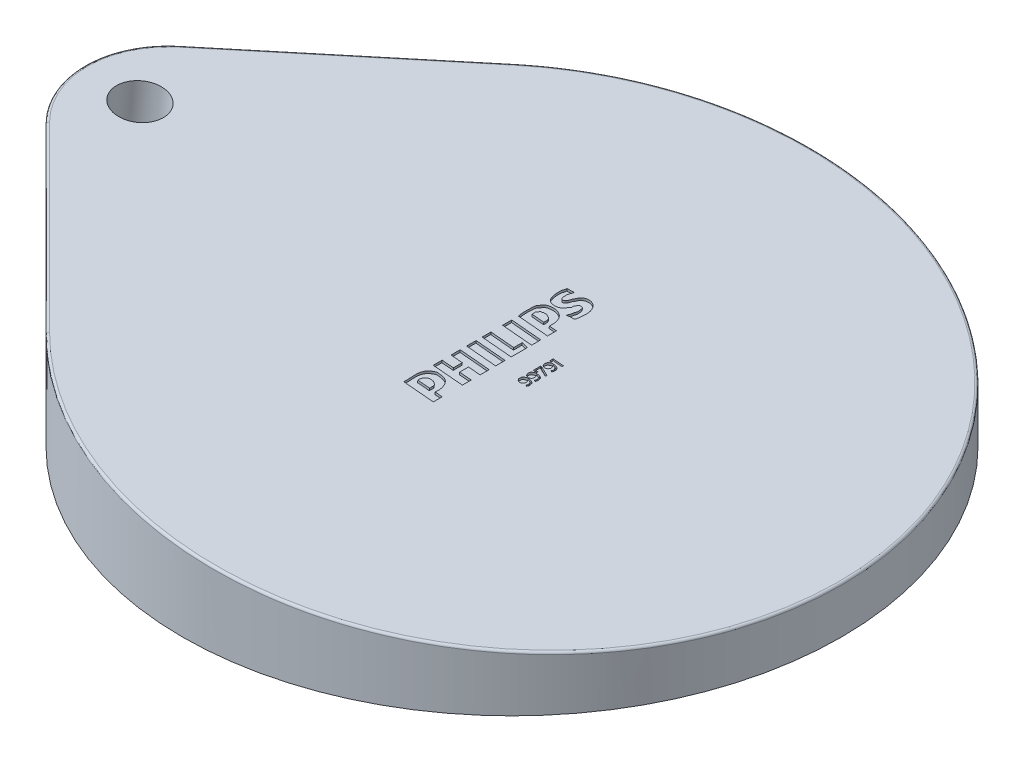
SolidWorks part; units mm, degrees
material "Copper"
ref_plane "Front Plane" through (0, 0, 0) normal (0, 0, 1) x (1, 0, 0)
ref_plane "Top Plane" through (0, 0, 0) normal (0, 1, 0) x (1, 0, 0)
ref_plane "Right Plane" through (0, 0, 0) normal (1, 0, 0) x (0, 0, -1)
sketch "Sketch14" plane through (0, 0, 0) normal (0, 0, 1) x (1, 0, 0)
  line L0 (0, -70) -> (-50, -70)
  line L1 (-70, 0) -> (-70, -50)
  line L2 (-69.75, 0) -> (-69.75, -49.75)
  line L3 (-49.75, -69.75) -> (0, -69.75)
  arc A0 (0, -70) -> (-70, 0) centre (0, 0) ccw
  arc A1 (-50, -70) -> (-70, -50) centre (-50, -50) cw
  circle A2 centre (-50, -50) radius 5
  arc A3 (0, -69.75) -> (-69.75, 0) centre (0, 0) ccw
  arc A4 (-69.75, -49.75) -> (-49.75, -69.75) centre (-49.75, -49.75) ccw
  dimension "D1" = 20
  dimension "D2" = 10
  dimension "D3" = 20
extrude "Boss-Extrude1" add sketch "Sketch14" along normal blind 25 contours A1 L0 A0 L1 A4 L2 A3 L3 region at (-25, -69.802, 0)
sketch "Sketch15" plane through (0, 0, 0) normal (0, 0, -1) x (-1, 0, 0)
  line L0 (69.75, 0) -> (69.75, -49.75)
  line L1 (49.75, -69.75) -> (0, -69.75)
  arc A0 (69.75, 0) -> (0, -69.75) centre (0, 0) ccw
  arc A1 (69.75, -49.75) -> (49.75, -69.75) centre (49.75, -49.75) cw
  dimension "D1" = 20
extrude "Boss-Extrude2" add sketch "Sketch15" against normal blind 17 contours A0 L1 A1 L0
sketch "Sketch16" plane through (0, 0, 17) normal (0, 0, 1) x (1, 0, 0)
  circle A0 centre (0, 0) radius 67.75
extrude "Boss-Extrude3" add sketch "Sketch16" along normal blind 8
fillet "Fillet1" radius 2 1 edges at (67.75, 0, 25)
fillet "Fillet5" radius 0.1 4 edges at (-24.875, -69.75, 25) (-63.8921, -63.8921, 25) (-69.75, -24.875, 25) (49.3207, 49.3207, 25)
sketch "Sketch18" plane through (0, 0, 0) normal (0, 0, -1) x (-1, 0, 0)
  line L0 (0, 0) -> (-49.4975, 49.4975)
  line L1 (0, 0) -> (64.1421, -64.1421)
  line L2 (-49.4975, 49.4975) -> (-22.8479, 76.1471)
  line L3 (-49.4975, 49.4975) -> (-71.4114, 27.5835)
  arc A0 (70, 0) -> (0, -70) centre (0, 0) ccw construction
  arc A1 (50, -70) -> (70, -50) centre (50, -50) ccw construction
sketch "Sketch19" plane through (0, 0, 25) normal (0, 0, 1) x (1, 0, 0)
  line L0 (0, 0) -> (49.4975, 49.4975)
  line L1 (0, 0) -> (-64.1421, -64.1421)
  line L2 (49.4975, 49.4975) -> (28.7907, 70.2043)
  line L3 (49.4975, 49.4975) -> (66.7686, 32.2263)
ref_plane "Plane1" through (49.4975, 49.4975, 0) normal (0.7071, 0.7071, 0) x (0, 0, -1)
sketch "Sketch20" plane through (49.4975, 49.4975, 0) normal (0.7071, 0.7071, 0) x (0, 0, -1)
  line L0 (0, 37.6882) -> (-25, 37.6882)
  line L1 (0, 0) -> (0, 37.6882) construction
  line L2 (-25, 70) -> (-25, -70) construction
  line L3 (0, -30.991) -> (-15, -30.991)
  line L5 (-15, -30.991) -> (-15, 37.6882)
sketch "Sketch21" plane through (0, 0, 0) normal (0, 0, -1) x (-1, 0, 0)
  line L0 (64.1421, -64.1421) -> (48.7013, -79.583)
  arc A0 (50, -70) -> (70, -50) centre (50, -50) ccw construction
ref_plane "Plane2" through (-0.5539, -0.5539, 8.3934) normal (-0.0657, -0.0657, 0.9957) x (0.9978, -0.0043, 0.0656)
sketch "Sketch23" plane through (-0.5539, -0.5539, 8.3934) normal (-0.0657, -0.0657, 0.9957) x (0.9978, -0.0043, 0.0656)
  line L1 (-71.9957, 85.0737) -> (75.8457, 85.0737)
  line L2 (-71.9957, 85.0737) -> (-71.9957, -81.3408)
  line L3 (-71.9957, -81.3408) -> (75.8457, -81.3408)
  line L4 (75.8457, 85.0737) -> (75.8457, -81.3408)
  line L5 (-71.9957, 85.0737) -> (75.8457, -81.3408) construction
  line L6 (-71.9957, -81.3408) -> (75.8457, 85.0737) construction
  point P0 (1.925, 1.8664)
extrude "Cut-Extrude1" cut sketch "Sketch23" against normal blind 20
fillet "Fillet6" radius 0.5 4 edges at (-64.1421, -64.1421, 0) (-70, -25, 2.1967) (-25, -70, 2.1967) (49.4975, 49.4975, 15)
sketch "Sketch25" plane through (0, 0, 17) normal (0, 0, 1) x (1, 0, 0)
  line L0 (-64.1421, -64.1421) -> (-56.0245, -56.0245)
  line L1 (0, 0) -> (-64.1421, -64.1421) construction
ref_plane "Plane3" through (0, 0, 0) normal (0, 0, -1) x (-1, 0, 0)
sketch "Sketch30" plane through (0, 0, 0) normal (0, 0, -1) x (-1, 0, 0)
  line L0 (48.7013, -79.583) -> (-64.9383, 34.0566)
  line L1 (-49.4975, 49.4975) -> (-71.4114, 27.5835) construction
  line L2 (-64.9383, 34.0566) -> (-49.4975, 49.4975)
  line L3 (-49.4975, 49.4975) -> (64.1421, -64.1421)
  line L4 (64.1421, -64.1421) -> (48.7013, -79.583)
ref_plane "Plane4" through (0, 0, 0) normal (-0.7071, 0.7071, 0) x (0, 0, 1)
sketch "Sketch32" plane through (0, 0, 0) normal (-0.7071, 0.7071, 0) x (0, 0, 1)
  line L0 (17, -79.2307) -> (-0.8396, -79.2307)
  line L1 (17, -90.7107) -> (17, -79.2307) construction
hole_wizard "Ø10.0mm Dowel Hole1" positions "Sketch34" profile "Sketch35" hole size "Ø10.0" standard "JIS" end condition through all
sketch "Sketch34" plane through (-0.5539, -0.5539, 8.3934) normal (0.0657, 0.0657, -0.9957) x (-0.9978, 0.0043, -0.0656)
  point P0 (55.4551, -55.8029)
sketch "Sketch35" plane through (-55.8892, -55.9957, 1.0823) normal (0.704, 0.704, 0.0929) x (-0.7071, 0.7071, 0)
  line L0 (0, 0) -> (0, 25.6617)
  line L1 (0, 25.6617) -> (5, 25.6617)
  line L2 (5, 25.6617) -> (5, 0)
  line L5 (5, 0) -> (0, 0)
  line L11 (0, -6.35) -> (0, 107.95) construction
  dimension "Thru Hole Dia." = 10
  dimension "Thru Hole Depth" = 25.6617
move or copy body "Body-Move/Copy1" bodies to move or copy 108 copy no rotation origin (0, 0, 12.5244) rotation axis (1, 0, 0) rotation angle 90
move or copy body "Body-Move/Copy2" bodies to move or copy 109 copy no rotation origin (0, 0, 12.5244) rotation axis (0, 1, 0) rotation angle 45
sketch "Sketch36" plane through (0.3755, 4.0229, 0) normal (0.0929, 0.9957, 0) x (0.9957, -0.0929, 0)
  line L0 (209.115, 125.4976) -> (-90.4887, 335.0225) construction
  line L1 (-1.9661, -27.2695) -> (-0.4649, -27.2695)
  line L2 (-0.4649, -27.2695) -> (-0.4649, -29.163)
  line L3 (-0.4649, -29.163) -> (-6.7662, -29.163)
  line L4 (-6.6535, -22.9931) -> (-0.4649, -22.9931)
  line L5 (-0.4649, -22.9931) -> (-0.4649, -21.106)
  line L6 (-0.4649, -21.106) -> (-2.9289, -21.106)
  line L7 (-2.9289, -21.106) -> (-2.9289, -19.2175)
  line L8 (-2.9289, -19.2175) -> (-0.4649, -19.2175)
  line L9 (-0.4649, -19.2175) -> (-0.4649, -17.2783)
  line L10 (-0.4649, -17.2783) -> (-6.6535, -17.2783)
  line L11 (-6.6535, -17.2783) -> (-6.6535, -19.2175)
  line L12 (-6.6535, -19.2175) -> (-4.2673, -19.2175)
  line L13 (-4.2673, -19.2175) -> (-4.2673, -21.106)
  line L14 (-4.2673, -21.106) -> (-6.6535, -21.106)
  line L15 (-6.6535, -21.106) -> (-6.6535, -22.9931)
  line L16 (-6.6535, -15.9111) -> (-0.4649, -15.9111)
  line L17 (-0.4649, -15.9111) -> (-0.4649, -13.8973)
  line L18 (-0.4649, -13.8973) -> (-6.6535, -13.8973)
  line L19 (-6.6535, -13.8973) -> (-6.6535, -15.9111)
  line L20 (-6.6535, -12.6141) -> (-6.6535, -10.7418)
  line L21 (-6.6535, -10.7418) -> (-1.8017, -10.7418)
  line L22 (-1.8017, -10.7418) -> (-1.8017, -8.9313)
  line L23 (-1.8017, -8.9313) -> (-0.4649, -9.1758)
  line L24 (-0.4649, -9.1758) -> (-0.4649, -12.6141)
  line L25 (-0.4649, -12.6141) -> (-6.6535, -12.6141)
  line L26 (-6.6535, -8.2717) -> (-6.6535, -6.3262)
  line L27 (-6.6535, -6.3262) -> (-0.4649, -6.3262)
  line L28 (-0.4649, -6.3262) -> (-0.4649, -8.2717)
  line L29 (-0.4649, -8.2717) -> (-6.6535, -8.2717)
  line L30 (-1.9661, -3.0074) -> (-0.4649, -3.0074)
  line L31 (-0.4649, -3.0074) -> (-0.4649, -4.8969)
  line L32 (-0.4649, -4.8969) -> (-6.6535, -4.8969)
  line L33 (-6.5763, 5.3472) -> (-5.2945, 5.5017)
  line L34 (-5.6594, -27.2695) -> (-3.1494, -27.2695)
  line L35 (-5.6594, -3.0074) -> (-3.1494, -3.0074)
  spline S0 degree 3 poles (-6.7662, -29.163) (-6.672, -28.1429) (-6.9728, -26.7336) (-6.5892, -24.9772) (-5.8847, -24.1952) (-5.2271, -23.695) (-4.5387, -23.75) (-3.914, -23.7336) (-2.1969, -24.1997) (-1.7788, -26.2583) (-1.9661, -27.2695) knots 0 0 0 0 0.259906 0.369029 0.441006 0.530161 0.563335 0.614973 0.691941 1 1 1 1
  spline S1 degree 3 poles (-6.6535, -4.8969) (-6.8589, -3.9026) (-6.8392, -2.5915) (-6.7291, -0.9759) (-6.2072, -0.3942) (-5.8981, 0.1621) (-5.0512, 0.4313) (-3.9547, 0.6243) (-2.042, -0.2796) (-1.8866, -2.0905) (-1.9661, -3.0074) knots 0 0 0 0 0.25849 0.34914 0.395592 0.457454 0.505063 0.616064 0.741541 1 1 1 1
  spline S2 degree 3 poles (-6.5763, 2.2393) (-6.6154, 2.5412) (-6.8219, 2.9495) (-6.7636, 3.6814) (-6.8713, 4.2683) (-6.6374, 4.8544) (-6.5547, 5.1688) (-6.5763, 5.3472) knots 0 0 0 0 0.291177 0.409261 0.692659 0.836782 1 1 1 1
  spline S3 degree 3 poles (-5.2945, 5.5017) (-5.1632, 5.2183) (-5.4857, 4.8481) (-5.5091, 4.1602) (-5.5601, 3.6311) (-5.4618, 3.1398) (-5.1972, 2.9189) (-4.8264, 2.9123) (-4.5828, 3.2997) (-4.3674, 3.6916) (-4.2835, 4.2045) (-4.0188, 4.5733) (-3.8755, 5.044) (-3.5901, 5.4384) (-3.2422, 5.7223) (-2.5672, 6.0264) (-1.5679, 5.9427) (-0.7798, 5.1024) (-0.4269, 4.2254) (-0.3431, 3.1653) (-0.4446, 2.1868) (-0.5227, 1.4638) (-0.6482, 0.9518) (-1.0735, 0.9933) (-1.4507, 0.9745) (-2.2784, 0.6524) (-1.9653, 1.1599) (-1.8705, 1.5207) (-1.8207, 2.0599) (-1.6323, 2.5269) (-1.6304, 3.045) (-1.7108, 3.4359) (-1.7275, 3.8756) (-2.0971, 3.9204) (-2.4194, 3.9897) (-2.7352, 3.7432) (-2.7449, 3.4017) (-3.0368, 3.0986) (-2.8616, 2.6258) (-3.2953, 2.4195) (-3.3417, 1.9477) (-3.7098, 1.472) (-4.1534, 1.1707) (-4.6775, 0.9963) (-5.1579, 0.9905) (-5.6651, 1.0735) (-6.2932, 1.37) (-6.5389, 1.8931) (-6.5763, 2.2393) knots 0 0 0 0 0.032815 0.052053 0.082166 0.097887 0.110043 0.121085 0.138188 0.15993 0.176609 0.199655 0.213707 0.235812 0.257471 0.267239 0.325372 0.361931 0.402174 0.437493 0.49032 0.518209 0.531461 0.544597 0.560728 0.589551 0.597859 0.618971 0.638803 0.661687 0.679729 0.699501 0.713559 0.723725 0.739274 0.753455 0.76493 0.778457 0.80129 0.808171 0.8315 0.85169 0.880232 0.894903 0.918103 0.937497 0.956998 1 1 1 1
  spline S4 degree 3 poles (-5.6594, -27.2695) (-5.693, -26.9753) (-5.6167, -26.5188) (-5.3166, -26.0232) (-5.0214, -25.7159) (-4.6278, -25.618) (-4.2599, -25.6852) (-3.8606, -25.6279) (-3.6357, -25.897) (-3.3913, -25.9756) (-3.2515, -26.1705) (-3.1218, -26.4058) (-3.1671, -26.8044) (-3.1399, -27.0791) (-3.1494, -27.2695) knots 0 0 0 0 0.18576 0.278271 0.362029 0.445926 0.518355 0.599299 0.677944 0.719014 0.755144 0.824482 0.881637 1 1 1 1
  spline S5 degree 3 poles (-5.6594, -3.0074) (-5.5999, -2.7733) (-5.7866, -2.3877) (-5.533, -2.0446) (-5.3955, -1.855) (-5.2992, -1.5517) (-4.958, -1.531) (-4.7171, -1.3839) (-4.45, -1.4003) (-4.1759, -1.3427) (-3.9236, -1.5021) (-3.6607, -1.5808) (-3.3644, -1.753) (-3.063, -2.2457) (-3.1904, -2.718) (-3.1494, -3.0074) knots 0 0 0 0 0.155513 0.211402 0.254101 0.304714 0.393275 0.435751 0.47848 0.556519 0.60064 0.658298 0.728618 0.809494 1 1 1 1
extrude "Cut-Extrude2" cut sketch "Sketch36" against normal blind 0.5
sketch "Sketch37" plane through (0.3755, 4.0229, 0) normal (0.0929, 0.9957, 0) x (0.9957, -0.0929, 0)
  line L0 (565.4535, 305.0482) -> (565.4535, 1670.3816) construction
  line L1 (4.6343, -12.3207) -> (3.9617, -12.3207)
  line L2 (3.9617, -12.3207) -> (3.9617, -10.7325)
  line L3 (3.9617, -10.7325) -> (4.141, -10.7325)
  line L4 (4.141, -10.7325) -> (6.1472, -11.5921)
  line L5 (6.1472, -11.5921) -> (6.1472, -11.9359)
  line L6 (6.1472, -11.9359) -> (4.2287, -11.1139)
  line L7 (4.2287, -11.1139) -> (4.2287, -12.0341)
  line L8 (4.2287, -12.0341) -> (4.6343, -12.0341)
  line L9 (4.6343, -12.0341) -> (4.6343, -12.3207)
  line L10 (3.9683, -8.8741) -> (3.9683, -8.0882)
  line L11 (3.9683, -8.0882) -> (6.139, -8.0882)
  line L12 (6.139, -8.0882) -> (6.139, -8.3993)
  line L13 (6.139, -8.3993) -> (4.2808, -8.3993)
  line L14 (4.2808, -8.3993) -> (4.2808, -8.8741)
  line L15 (4.2808, -8.8741) -> (3.9683, -8.8741)
  spline S0 degree 3 poles (3.9237, -15.3814) (3.9582, -15.1541) (3.9388, -14.9096) (4.0405, -14.6382) (4.2453, -14.4871) (4.4596, -14.3106) (4.77, -14.2598) (5.1318, -14.2566) (5.4852, -14.2793) (5.7955, -14.4437) (6.0363, -14.6897) (6.1457, -15.0308) (6.1545, -15.4042) (6.0827, -15.607) (5.9971, -15.8434) (5.9072, -15.739) (5.8498, -15.6931) (5.7174, -15.6513) (5.8009, -15.5585) (5.8393, -15.4266) (5.8672, -15.223) (5.828, -14.9825) (5.711, -14.7669) (5.4875, -14.6146) (5.3046, -14.6066) (4.9899, -14.4713) (5.0669, -14.6327) (5.1769, -14.6611) (5.1842, -14.7921) (5.2607, -14.9106) (5.3095, -15.0714) (5.2955, -15.2583) (5.2938, -15.435) (5.1966, -15.5512) (5.1158, -15.6846) (4.9868, -15.8022) (4.8136, -15.8976) (4.612, -15.8991) (4.4104, -15.8953) (4.2528, -15.7983) (4.1152, -15.7056) (4.0356, -15.5487) (3.9237, -15.3814) (3.9582, -15.1541) (3.9388, -14.9096) knots -0.066071 -0.047148 -0.023333 0 0.028016 0.061139 0.092919 0.113702 0.155297 0.195615 0.239097 0.273863 0.313563 0.353136 0.395147 0.432082 0.445561 0.452869 0.468973 0.479099 0.484547 0.503801 0.529157 0.55279 0.586284 0.61121 0.637349 0.664788 0.673144 0.68457 0.700527 0.710971 0.733418 0.755818 0.775619 0.791173 0.805951 0.829112 0.850055 0.871695 0.897159 0.917267 0.933929 0.952852 0.976667 1 1.028016 1.061139 1.092919 only from (3.9487, -15.1696) to (3.9487, -15.1696)
  spline S1 degree 3 poles (3.9284, -13.5832) (3.963, -13.3558) (3.9436, -13.1113) (4.0452, -12.84) (4.2501, -12.6889) (4.4644, -12.5123) (4.7748, -12.4616) (5.1365, -12.4584) (5.49, -12.4811) (5.8002, -12.6454) (6.041, -12.8914) (6.1505, -13.2326) (6.1592, -13.606) (6.0875, -13.8087) (6.0019, -14.0452) (5.912, -13.9408) (5.8546, -13.8948) (5.7222, -13.853) (5.8056, -13.7603) (5.844, -13.6283) (5.8719, -13.4247) (5.8328, -13.1843) (5.7157, -12.9687) (5.4923, -12.8164) (5.3093, -12.8084) (4.9946, -12.673) (5.0716, -12.8344) (5.1816, -12.8629) (5.189, -12.9939) (5.2654, -13.1123) (5.3142, -13.2732) (5.3003, -13.4601) (5.2986, -13.6368) (5.2014, -13.7529) (5.1205, -13.8863) (4.9915, -14.004) (4.8184, -14.0993) (4.6168, -14.1008) (4.4151, -14.0971) (4.2575, -14.0001) (4.12, -13.9073) (4.0403, -13.7505) (3.9284, -13.5832) (3.963, -13.3558) (3.9436, -13.1113) knots -0.066071 -0.047148 -0.023333 0 0.028016 0.061139 0.092919 0.113702 0.155297 0.195615 0.239097 0.273863 0.313563 0.353136 0.395147 0.432082 0.445561 0.452869 0.468973 0.479099 0.484547 0.503801 0.529157 0.55279 0.586284 0.61121 0.637349 0.664788 0.673144 0.68457 0.700527 0.710971 0.733418 0.755818 0.775619 0.791173 0.805951 0.829112 0.850055 0.871695 0.897159 0.917267 0.933929 0.952852 0.976667 1 1.028016 1.061139 1.092919 only from (3.9535, -13.3714) to (3.9535, -13.3714)
  spline S2 degree 3 poles (3.935, -10.0683) (3.9696, -9.841) (3.9502, -9.5965) (4.0518, -9.3251) (4.2567, -9.174) (4.471, -8.9975) (4.7814, -8.9467) (5.1431, -8.9435) (5.4966, -8.9662) (5.8068, -9.1306) (6.0476, -9.3766) (6.1571, -9.7177) (6.1658, -10.0911) (6.0941, -10.2939) (6.0085, -10.5303) (5.9186, -10.4259) (5.8612, -10.38) (5.7288, -10.3382) (5.8122, -10.2454) (5.8506, -10.1135) (5.8785, -9.9099) (5.8394, -9.6694) (5.7223, -9.4538) (5.4989, -9.3015) (5.3159, -9.2935) (5.0012, -9.1582) (5.0782, -9.3196) (5.1882, -9.348) (5.1956, -9.479) (5.272, -9.5975) (5.3208, -9.7583) (5.3069, -9.9452) (5.3052, -10.1219) (5.208, -10.2381) (5.1271, -10.3715) (4.9981, -10.4891) (4.825, -10.5845) (4.6234, -10.586) (4.4217, -10.5822) (4.2641, -10.4852) (4.1266, -10.3925) (4.0469, -10.2357) (3.935, -10.0683) (3.9696, -9.841) (3.9502, -9.5965) knots -0.066071 -0.047148 -0.023333 0 0.028016 0.061139 0.092919 0.113702 0.155297 0.195615 0.239097 0.273863 0.313563 0.353136 0.395147 0.432082 0.445561 0.452869 0.468973 0.479099 0.484547 0.503801 0.529157 0.55279 0.586284 0.61121 0.637349 0.664788 0.673144 0.68457 0.700527 0.710971 0.733418 0.755818 0.775619 0.791173 0.805951 0.829112 0.850055 0.871695 0.897159 0.917267 0.933929 0.952852 0.976667 1 1.028016 1.061139 1.092919 only from (3.9601, -9.8565) to (3.9601, -9.8565)
extrude "Cut-Extrude3" cut sketch "Sketch37" against normal blind 0.5
